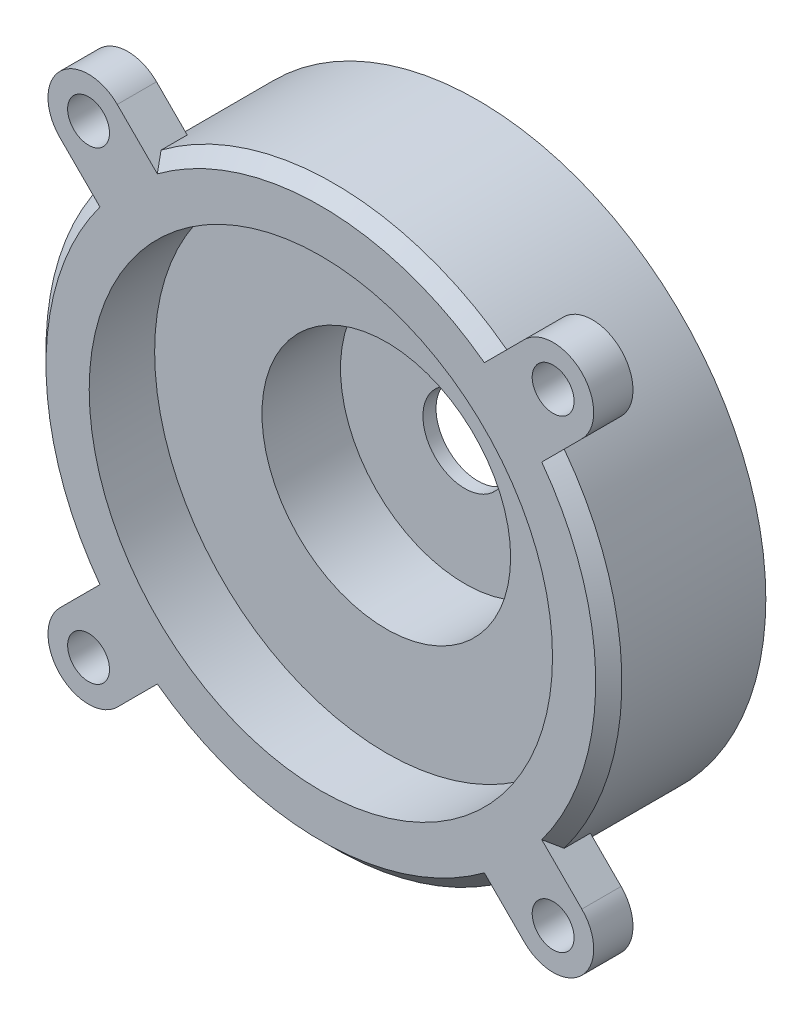
SolidWorks part; units mm, degrees
ref_plane "Front Plane" through (0, 0, 0) normal (0, 0, 1) x (1, 0, 0)
ref_plane "Top Plane" through (0, 0, 0) normal (0, 1, 0) x (1, 0, 0)
ref_plane "Right Plane" through (0, 0, 0) normal (1, 0, 0) x (0, 0, -1)
sketch "Sketch1" plane through (0, 0, 0) normal (0, 0, 1) x (1, 0, 0)
  circle A0 centre (0, 0) radius 22
  dimension "D1" = 44
extrude "Boss-Extrude1" add sketch "Sketch1" along normal mid plane 12
chamfer "Chamfer1" distance 1 angle 45 1 edges at (22, 0, 6)
sketch "Sketch8" plane through (0, 0, 6) normal (0, 0, 1) x (1, 0, 0)
  line L1 (15.5563, 19.9404) -> (12.4945, 16.8786)
  line L6 (19.9404, 15.5563) -> (16.8786, 12.4945)
  line L7 (12.4945, 16.8786) -> (16.8786, 12.4945)
  line L8 (19.9404, -15.5563) -> (16.8786, -12.4945)
  line L9 (15.5563, -19.9404) -> (12.4945, -16.8786)
  line L10 (16.8786, -12.4945) -> (12.4945, -16.8786)
  line L11 (-15.5563, -19.9404) -> (-12.4945, -16.8786)
  line L12 (-19.9404, -15.5563) -> (-16.8786, -12.4945)
  line L13 (-12.4945, -16.8786) -> (-16.8786, -12.4945)
  line L14 (-19.9404, 15.5563) -> (-16.8786, 12.4945)
  line L15 (-15.5563, 19.9404) -> (-12.4945, 16.8786)
  line L16 (-16.8786, 12.4945) -> (-12.4945, 16.8786)
  circle A2 centre (17.7484, 17.7484) radius 1.6
  circle A3 centre (17.7484, -17.7484) radius 1.6
  arc A4 (19.9404, 15.5563) -> (15.5563, 19.9404) centre (17.7484, 17.7484) ccw
  arc A5 (15.5563, -19.9404) -> (19.9404, -15.5563) centre (17.7484, -17.7484) ccw
  circle A6 centre (0, 0) radius 21 construction
  circle A7 centre (-17.7484, -17.7484) radius 1.6
  arc A8 (-19.9404, -15.5563) -> (-15.5563, -19.9404) centre (-17.7484, -17.7484) ccw
  circle A9 centre (-17.7484, 17.7484) radius 1.6
  arc A10 (-15.5563, 19.9404) -> (-19.9404, 15.5563) centre (-17.7484, 17.7484) ccw
  point P9 (0, 0)
  point P31 (0, 0)
  dimension "D1" = 4
extrude "Boss-Extrude2" add sketch "Sketch8" against normal blind 3
sketch "Sketch9" plane through (0, 0, 6) normal (0, 0, 1) x (1, 0, 0)
  circle A0 centre (0, 0) radius 17.7
extrude "Cut-Extrude1" cut sketch "Sketch9" against normal blind 5
sketch "Sketch10" plane through (0, 0, 1) normal (0, 0, 1) x (1, 0, 0)
  circle A0 centre (0, 0) radius 9.5
extrude "Cut-Extrude2" cut sketch "Sketch10" against normal blind 6
sketch "Sketch11" plane through (0, 0, -5) normal (0, 0, 1) x (1, 0, 0)
  circle A0 centre (0, 0) radius 3.2
extrude "Cut-Extrude3" cut sketch "Sketch11" against normal blind 1
